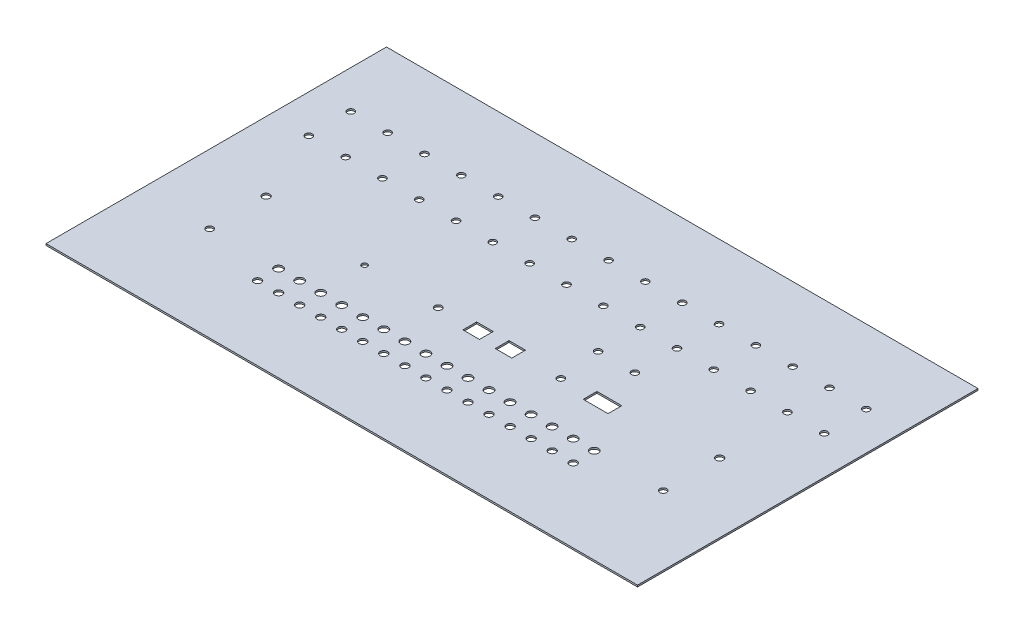
SolidWorks part; units mm, degrees
ref_plane "Front Plane" through (0, 0, 0) normal (0, 0, 1) x (1, 0, 0)
ref_plane "Top Plane" through (0, 0, 0) normal (0, 1, 0) x (1, 0, 0)
ref_plane "Right Plane" through (0, 0, 0) normal (1, 0, 0) x (0, 0, -1)
sketch "Sketch1" plane through (0, 0, 0) normal (0, 1, 0) x (1, 0, 0)
  line L1 (281.15, -161.825) -> (-281.15, -161.825)
  line L2 (281.15, -161.825) -> (281.15, 161.825)
  line L3 (281.15, 161.825) -> (-281.15, 161.825)
  line L4 (-281.15, -161.825) -> (-281.15, 161.825)
  line L5 (281.15, -161.825) -> (-281.15, 161.825) construction
  line L6 (281.15, 161.825) -> (-281.15, -161.825) construction
  point P0 (0, 0)
  dimension "D1" = 323.65
  dimension "D2" = 562.3
extrude "Boss-Extrude1" add sketch "Sketch1" along normal blind 1.5875
sketch "Sketch2" plane through (0, 1.5875, 0) normal (0, 1, 0) x (1, 0, 0)
  line L0 (-281.15, 161.825) -> (-281.15, -161.825) construction
  line L1 (281.15, 161.825) -> (-281.15, 161.825) construction
  circle A0 centre (-245, 91.825) radius 3.25
  dimension "D1" = 6.5
  dimension "D2" = 36.15
  dimension "D3" = 70
extrude "Cut-Extrude1" cut sketch "Sketch2" against normal up to next
sketch "Sketch3" plane through (0, 1.5875, 0) normal (0, 1, 0) x (1, 0, 0)
  circle A0 centre (-245, 91.825) radius 9.5
  point P3 (0, 0)
  point P4 (0, 0)
  point P5 (-245, 48.9357)
  point P6 (0, 0)
pattern_linear "LPattern1" count 15 spacing 35 along (1, 0, 0) count 2 spacing 40 along (0, 0, 1) of "Cut-Extrude1"
sketch "Sketch6" plane through (0, 1.5875, 0) normal (0, 1, 0) x (1, 0, 0)
  line L0 (-281.15, 161.825) -> (-281.15, -161.825) construction
  line L1 (-281.15, -161.825) -> (281.15, -161.825) construction
  circle A0 centre (-150, -91.825) radius 3.5
  point P4 (0, 0)
  dimension "D1" = 131.15
  dimension "D2" = 70
extrude "Cut-Extrude2" cut sketch "Sketch6" against normal up to next
pattern_linear "LPattern2" count 16 spacing 20 along (1, 0, 0) of "Cut-Extrude2"
sketch "Sketch7" plane through (0, 1.5875, 0) normal (0, 1, 0) x (1, 0, 0)
  line L0 (-281.15, 161.825) -> (-281.15, -161.825) construction
  circle A0 centre (-150, -71.825) radius 4
  circle A1 centre (-150, -91.825) radius 3.5 construction
  dimension "D1" = 131.15
  dimension "D2" = 20
extrude "Cut-Extrude3" cut sketch "Sketch7" against normal up to next
pattern_linear "LPattern3" count 16 spacing 20 along (1, 0, 0) of "Cut-Extrude3"
sketch "Sketch8" plane through (0, 1.5875, 0) normal (0, 1, 0) x (1, 0, 0)
  line L1 (-281.15, 161.825) -> (-281.15, -161.825) construction
  line L2 (-281.15, -161.825) -> (281.15, -161.825) construction
  circle A0 centre (-215.575, -71.825) radius 3.3
  dimension "D1" = 90
  dimension "D2" = 65.575
extrude "Cut-Extrude4" cut sketch "Sketch8" against normal up to next
sketch "Sketch10" plane through (0, 1.5875, 0) normal (0, 1, 0) x (1, 0, 0)
  line L0 (281.15, -161.825) -> (281.15, 161.825) construction
  line L1 (-281.15, -161.825) -> (281.15, -161.825) construction
  circle A0 centre (215.575, -71.825) radius 3.25
  dimension "D1" = 65.575
  dimension "D2" = 90
extrude "Cut-Extrude5" cut sketch "Sketch10" against normal up to next
sketch "Sketch11" plane through (0, 1.5875, 0) normal (0, 1, 0) x (1, 0, 0)
  line L0 (281.15, 161.825) -> (-281.15, 161.825) construction
  circle A0 centre (74.5943, -28.175) radius 3.3
  dimension "D1" = 190
extrude "Cut-Extrude6" cut sketch "Sketch11" against normal up to next
sketch "Sketch12" plane through (0, 1.5875, 0) normal (0, 1, 0) x (1, 0, 0)
  text T0 "BPM Control\r\n\r\n"
  point P1 (94.8416, 7.4779)
  point P2 (96.5556, 21.6182)
  point P3 (59.6919, 22.0295)
  point P4 (62.8056, -7.723)
  point P5 (60.6519, -17.1912)
sketch "Sketch13" plane through (0, 1.5875, 0) normal (0, 1, 0) x (1, 0, 0)
  text T0 "Channel Select"
  point P1 (-231.1255, -60.7323)
sketch "Sketch14" plane through (0, 1.5875, 0) normal (0, 1, 0) x (1, 0, 0)
  text T0 "Master Volume\r\n"
  point P1 (196.8229, -41.7987)
  point P2 (197.6878, -59.7951)
sketch "Sketch15" plane through (0, 1.5875, 0) normal (0, 1, 0) x (1, 0, 0)
  line L0 (281.15, 161.825) -> (-281.15, 161.825) construction
  line L1 (126.0074, -34.715) -> (102.3974, -34.715)
  line L2 (126.0074, -34.715) -> (126.0074, -21.635)
  line L3 (126.0074, -21.635) -> (102.3974, -21.635)
  line L4 (102.3974, -34.715) -> (102.3974, -21.635)
  line L5 (126.0074, -34.715) -> (102.3974, -21.635) construction
  line L6 (126.0074, -21.635) -> (102.3974, -34.715) construction
  point P0 (114.2024, -28.175)
  dimension "D1" = 13.08
  dimension "D2" = 23.61
  dimension "D3" = 190
extrude "Cut-Extrude7" cut sketch "Sketch15" against normal up to next
sketch "Sketch16" plane through (0, 1.5875, 0) normal (0, 1, 0) x (1, 0, 0)
  line L0 (281.15, 161.825) -> (-281.15, 161.825) construction
  circle A0 centre (-41.9525, -28.175) radius 3.3
  point P6 (0, 0)
  dimension "D1" = 190
extrude "Cut-Extrude8" cut sketch "Sketch16" against normal up to next contours A0
sketch "Sketch17" plane through (0, 1.5875, 0) normal (0, 1, 0) x (1, 0, 0)
  text T0 "Loop Back Control\r\n"
  point P1 (-61.0428, 20.2719)
  point P2 (-60.5865, -5.4569)
  point P3 (-60.7251, -17.544)
sketch "Sketch18" plane through (0, 1.5875, 0) normal (0, 1, 0) x (1, 0, 0)
  line L0 (102.3974, -34.715) -> (126.0074, -34.715) construction
  line L1 (3.7875, -34.715) -> (-11.9525, -34.715)
  line L2 (3.7875, -34.715) -> (3.7875, -21.635)
  line L3 (3.7875, -21.635) -> (-11.9525, -21.635)
  line L4 (-11.9525, -34.715) -> (-11.9525, -21.635)
  line L5 (3.7875, -34.715) -> (-11.9525, -21.635) construction
  line L6 (3.7875, -21.635) -> (-11.9525, -34.715) construction
  point P0 (-4.0825, -28.175)
  point P7 (0, 0)
  point P9 (0, 0)
  dimension "D1" = 13.08
  dimension "D2" = 15.74
  dimension "D3" = 0
extrude "Cut-Extrude9" cut sketch "Sketch18" against normal up to next
sketch "Sketch19" plane through (0, 1.5875, 0) normal (0, 1, 0) x (1, 0, 0)
  line L1 (34.5275, -34.715) -> (18.7875, -34.715)
  line L2 (34.5275, -34.715) -> (34.5275, -21.635)
  line L3 (34.5275, -21.635) -> (18.7875, -21.635)
  line L4 (18.7875, -34.715) -> (18.7875, -21.635)
  line L5 (34.5275, -34.715) -> (18.7875, -21.635) construction
  line L6 (34.5275, -21.635) -> (18.7875, -34.715) construction
  line L7 (-11.9525, -34.715) -> (3.7875, -34.715) construction
  line L8 (3.7875, -34.715) -> (3.7875, -21.635) construction
  point P0 (26.6575, -28.175)
  point P5 (0, 0)
  dimension "D4" = 15
  dimension "D1" = 13.08
  dimension "D2" = 15.74
  dimension "D3" = 0
extrude "Cut-Extrude10" cut sketch "Sketch19" against normal up to next
sketch "Sketch20" plane through (0, 1.5875, 0) normal (0, 1, 0) x (1, 0, 0)
  text T0 "Loop Back"
  point P1 (0, 0)
  point P2 (-17.6101, -4.669)
  point P3 (-15.9115, -29.5624)
  point P4 (-14.8559, -14.7213)
  point P5 (-17.6786, -42.2428)
sketch "Sketch21" plane through (0, 1.5875, 0) normal (0, 1, 0) x (1, 0, 0)
  text T0 "Current Position"
  point P1 (14.8957, -5.4249)
  point P2 (0, 0)
  point P3 (0, 0)
  point P4 (12.0687, -4.5517)
  point P5 (14.1014, -28.2526)
  point P6 (0, 0)
  point P7 (0, 0)
  point P8 (0, 0)
  point P9 (13.9809, -29.9104)
  point P10 (13.3714, -42.5957)
sketch "Sketch22" plane through (0, 1.5875, 0) normal (0, 1, 0) x (1, 0, 0)
  line L0 (281.15, 161.825) -> (-281.15, 161.825) construction
  circle A0 centre (-111.9525, -28.175) radius 2.605
  circle A2 centre (-41.9525, -28.175) radius 3.3 construction
  point P2 (0, 0)
  dimension "D1" = 190
  dimension "D2" = 70
extrude "Cut-Extrude11" cut sketch "Sketch22" against normal up to next
sketch "Sketch23" plane through (0, 1.5875, 0) normal (0, 1, 0) x (1, 0, 0)
  text T0 "Measure Select"
  point P1 (-130.6451, 20.5519)
  point P2 (-130.7088, 7.7923)
  point P3 (-126.3932, 0)
  point P4 (-126.2518, -9.9253)
  point P5 (-125.6477, -19.3082)
sketch "Sketch24" plane through (0, 1.5875, 0) normal (0, 1, 0) x (1, 0, 0)
  line L0 (-281.15, 161.825) -> (-281.15, -161.825) construction
  line L1 (281.15, 161.825) -> (-281.15, 161.825) construction
  circle A0 centre (-215.57, -18.175) radius 3.5
  text T0 "Start/Stop"
  point P7 (-223.1947, 0)
  point P8 (-223.1947, -7.8475)
  dimension "D1" = 65.58
  dimension "D2" = 180
extrude "Cut-Extrude12" cut sketch "Sketch24" against normal up to next contours A0
sketch "Sketch25" plane through (0, 1.5875, 0) normal (0, 1, 0) x (1, 0, 0)
  text T0 "Start/Stop\r\n"
  point P1 (-223.6278, -4.2707)
  point P2 (0, 0)
  point P3 (-224.8371, -9.1079)
sketch "Sketch26" plane through (0, 1.5875, 0) normal (0, 1, 0) x (1, 0, 0)
  line L0 (281.15, -161.825) -> (281.15, 161.825) construction
  line L1 (281.15, 161.825) -> (-281.15, 161.825) construction
  circle A0 centre (215.57, -18.175) radius 3.5
  dimension "D1" = 65.58
  dimension "D2" = 180
extrude "Cut-Extrude13" cut sketch "Sketch26" against normal up to next
sketch "Sketch27" plane through (0, 1.5875, 0) normal (0, 1, 0) x (1, 0, 0)
  text T0 "Reset"
  point P1 (204.2667, -6.565)
  point P2 (0, 0)
  point P3 (207.3159, -8.977)
sketch "Sketch28" plane through (0, 1.5875, 0) normal (0, 1, 0) x (1, 0, 0)
  line L0 (281.15, -161.825) -> (281.15, 161.825) construction
  circle A0 centre (70, 11.825) radius 3.25
  circle A1 centre (70, 51.825) radius 3.25 construction
  dimension "D1" = 40
  dimension "D2" = 211.15
extrude "Cut-Extrude14" cut sketch "Sketch28" against normal up to next
sketch "Sketch29" plane through (0, 1.5875, 0) normal (0, 1, 0) x (1, 0, 0)
  circle A0 centre (105, 11.825) radius 3.25
  circle A1 centre (70, 11.825) radius 3.25 construction
  circle A2 centre (105, 51.825) radius 3.25 construction
  dimension "D1" = 35
  dimension "D2" = 40
extrude "Cut-Extrude15" cut sketch "Sketch29" against normal up to next
